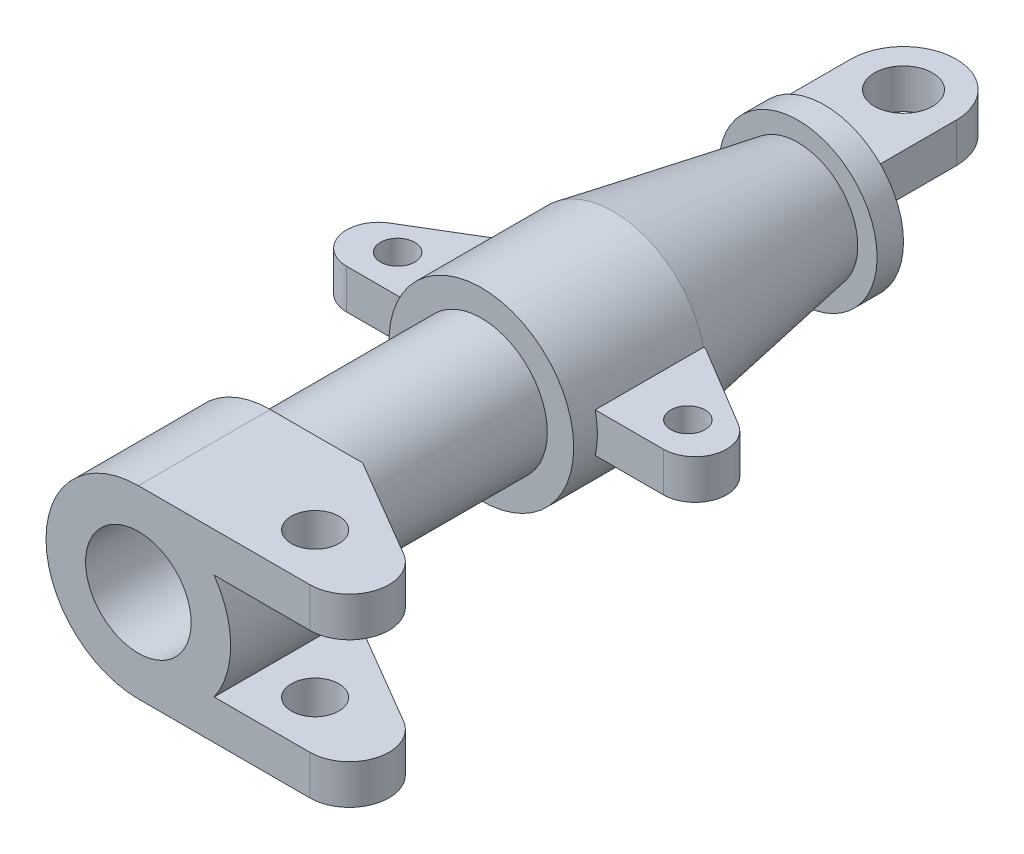
SolidWorks part; units mm, degrees
ref_plane "Front Plane" through (0, 0, 0) normal (0, 0, 1) x (1, 0, 0)
ref_plane "Top Plane" through (0, 0, 0) normal (0, 1, 0) x (1, 0, 0)
ref_plane "Right Plane" through (0, 0, 0) normal (1, 0, 0) x (0, 0, -1)
sketch "Sketch1" plane through (0, 0, 0) normal (0, 1, 0) x (1, 0, 0)
  line L0 (0, 0) -> (0, 182.677) construction
  line L1 (0, 0) -> (-35, 0)
  line L2 (-35, 0) -> (-35, 50)
  line L3 (-35, 50) -> (-25, 50)
  line L4 (-25, 50) -> (-25, 130)
  line L5 (-25, 130) -> (-35, 130)
  line L6 (-35, 130) -> (-35, 180)
  line L7 (-35, 180) -> (-22.6571, 250)
  line L8 (-22.6571, 250) -> (-30, 250)
  line L9 (-30, 250) -> (-30, 260)
  line L10 (-30, 260) -> (0, 260)
  line L11 (-20, 0) -> (-20, 235)
  line L12 (-20, 235) -> (0, 235)
  line L13 (0, 235) -> (0, 260)
  dimension "D1" = 235
  dimension "D2" = 40
  dimension "D3" = 70
  dimension "D4" = 50
  dimension "D5" = 50
  dimension "D6" = 70
  dimension "D7" = 10
  dimension "D8" = 60
  dimension "D9" = 10
  dimension "D10" = 50
  dimension "D11" = 80
  dimension "D12" = 70
revolve "Revolve1" add sketch "Sketch1" angle 360 about L0 region at (-23.503, 0, -143.7075)
sketch "Sketch2" plane through (0, 0, 0) normal (0, 1, 0) x (1, 0, 0)
  line L0 (-35, 138.9789) -> (-60, 138.9789)
  line L1 (-35, 180) -> (-35, 130) construction
  line L2 (-66.1805, 161.2649) -> (-35, 180)
  line L3 (-35, 180) -> (-35, 138.9789)
  line L4 (35, 180) -> (-35, 180) construction
  line L5 (0, 180) -> (0, 198.0618) construction
  line L6 (-35, 180) -> (-25, 180)
  line L7 (-25, 180) -> (-25, 138.9789)
  line L8 (-25, 138.9789) -> (-35, 138.9789)
  line L9 (-25, 130) -> (-25, 50) construction
  line L10 (25, 138.9789) -> (35, 138.9789)
  line L11 (25, 180) -> (25, 138.9789)
  line L12 (35, 180) -> (25, 180)
  line L13 (35, 180) -> (35, 138.9789)
  line L14 (66.1805, 161.2649) -> (35, 180)
  line L15 (35, 138.9789) -> (60, 138.9789)
  arc A0 (-60, 138.9789) -> (-66.1805, 161.2649) centre (-60, 150.9789) cw
  circle A1 centre (-55, 153.2689) radius 6.5
  arc A2 (60, 138.9789) -> (66.1805, 161.2649) centre (60, 150.9789) ccw
  circle A3 centre (55, 153.2689) radius 6.5
  dimension "D1" = 12
  dimension "D4" = 14.29
  dimension "D6" = 13
  dimension "D2" = 31
  dimension "D3" = 60
  dimension "D5" = 55
extrude "Boss-Extrude1" add sketch "Sketch2" along normal mid plane 15 contours A0 L0 L3 L2 A1 | L8 L7 L6 L3 | L13 L12 L11 L10 | L15 A2 L14 L13 A3 region at (-47.5, 0, -139.5313) region at (-30, 0, -159.4894) region at (30, 0, -159.4894) region at (35.5524, 0, -159.4894)
sketch "Sketch3" plane through (0, 0, 0) normal (0, 1, 0) x (1, 0, 0)
  line L0 (-20, 0) -> (20, 0) construction
  line L1 (-20, 0) -> (20, 0)
  line L2 (20, 0) -> (20, 85.7984) construction
  line L3 (0, 0) -> (0, 116.1441) construction
  line L4 (35, 0) -> (65, 0)
  line L5 (72.5926, 27.9365) -> (35, 50)
  line L6 (35, 50) -> (24.5873, 50)
  line L7 (35, 50) -> (-35, 50) construction
  line L8 (24.5873, 50) -> (24.5873, 0)
  line L9 (-35, 0) -> (35, 0) construction
  line L10 (24.5873, 0) -> (35, 0)
  arc A0 (65, 0) -> (72.5926, 27.9365) centre (65, 15) ccw
  circle A1 centre (48, 19) radius 9
  dimension "D1" = 15
  dimension "D3" = 18
  dimension "D5" = 17
  dimension "D2" = 65
  dimension "D4" = 19
extrude "Boss-Extrude2" add sketch "Sketch3" along normal through all and the other way through all contours L4 A0 L5 L6 L8 L10 A1 region at (29.7936, 0, -0.7464)
sketch "Sketch4" plane through (0, 35, 0) normal (0, 1, 0) x (1, 0, 0)
  line L2 (24.5873, 50) -> (-35, 50) construction
  line L4 (0, 0) -> (0, 50) construction
  line L5 (24.5873, 50) -> (0, 50)
  line L6 (0, 50) -> (0, 0)
  line L7 (0, 0) -> (24.5873, 0)
  line L8 (24.5873, 0) -> (24.5873, 50)
extrude "Boss-Extrude3" add sketch "Sketch4" against normal up to surface contours L8 L5 L6 L7 up to face at (-5.2064, 0, -25)
mirror "Mirror1" about plane through (0, 0, 0) normal (0, 1, 0) of "Boss-Extrude3"
sketch "Sketch5" plane through (0, 0, -50) normal (0, 0, -1) x (-1, 0, 0)
  line L0 (-35, 35) -> (-35, -35) construction
  line L1 (-90.1738, -20) -> (-35, -20)
  line L2 (-90.1738, -20) -> (-90.1738, 20)
  line L3 (-90.1738, 20) -> (-35, 20)
  line L4 (-35, -20) -> (-35, 20)
  line L5 (-90.1738, -20) -> (-35, 20) construction
  line L6 (-90.1738, 20) -> (-35, -20) construction
  line L7 (-72.5926, 35) -> (-35, 35) construction
  line L8 (-35, -20) -> (-28.7228, -20)
  line L9 (-35, 20) -> (-28.7228, 20)
  circle A1 centre (0, 0) radius 35
  point P0 (-62.5869, 0)
  line M4 (-35, 35) -> (-35, -35)
  dimension "D1" = 15
extrude "Cut-Extrude1" cut sketch "Sketch5" against normal through all contours L3 L2 L1 L4 M4 | A1 L9 M4 | A1 L4 L8 region at (62.5869, 0, -50) region at (33.1498, -15.0941, -50) region at (33.1498, 15.0941, -50)
sketch "Sketch6" plane through (0, 0, 0) normal (0, 1, 0) x (0, 0, -1)
  line L0 (260, -30) -> (260, 30) construction
  line L1 (260, -30) -> (260, 30)
  line L2 (230, 0) -> (290, 0) construction
  line L3 (230, 20) -> (290, 20)
  line L4 (230, -20) -> (290, -20)
  arc A0 (230, 20) -> (230, -20) centre (230, 0) ccw
  arc A1 (290, -20) -> (290, 20) centre (290, 0) ccw
  circle A2 centre (290, 0) radius 11
  point P4 (260, 0)
  dimension "D1" = 20
  dimension "D2" = 50
  dimension "D3" = 22
extrude "Boss-Extrude4" add sketch "Sketch6" along normal blind 20 contours L4 A1 L3 L1 A2 region at (0, 0, -260.6403)
extrude "Cut-Extrude2" cut sketch "Sketch6<3>" along normal blind 5 contours L4 A1 L3 L1 A2 region at (0, 0, -260.6403)
sketch "Sketch6<3>" plane through (0, 0, 0) normal (0, 1, 0) x (0, 0, -1) same geometry as "Sketch6"
